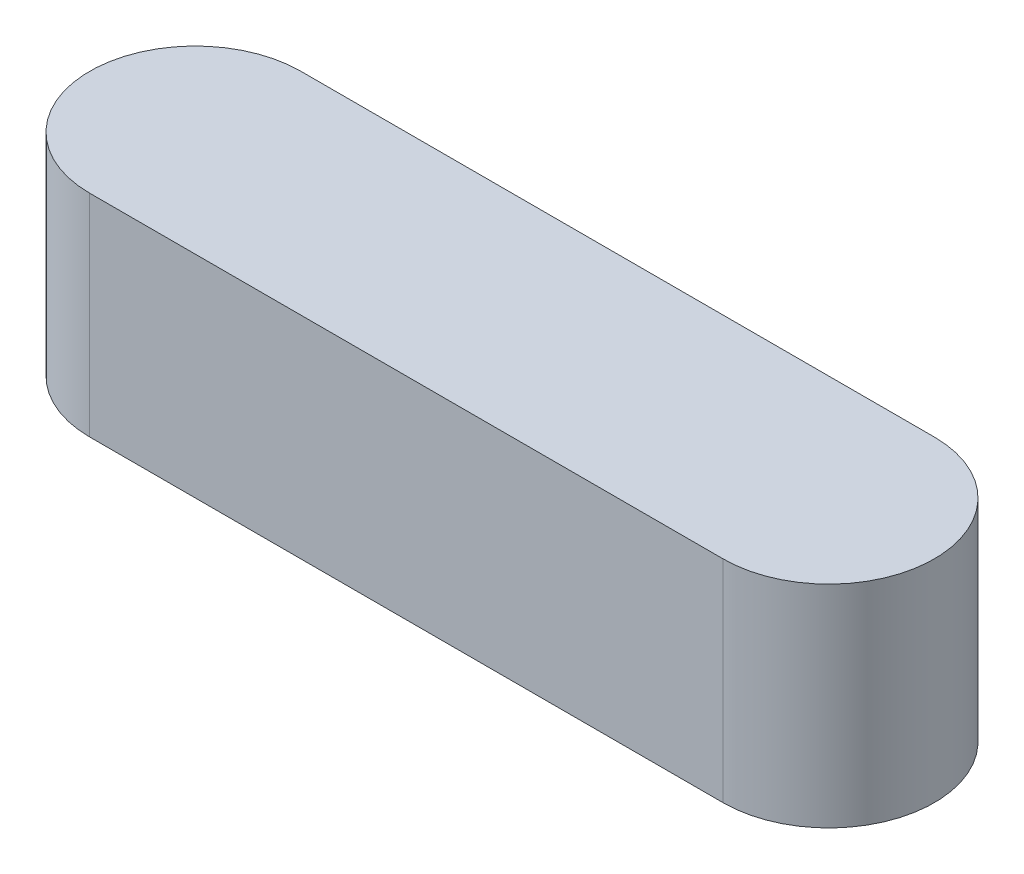
SolidWorks part; units mm, degrees
ref_plane "Front Plane" through (0, 0, 0) normal (0, 0, 1) x (1, 0, 0)
ref_plane "Top Plane" through (0, 0, 0) normal (0, 1, 0) x (1, 0, 0)
ref_plane "Right Plane" through (0, 0, 0) normal (1, 0, 0) x (0, 0, -1)
ref_axis "X AXIS" through (-88.99, 0, 0) along (1, 0, 0)
ref_axis "Y AXIS" through (0, 55, 0) along (0, -1, 0)
ref_axis "Z AXIS" through (0, 0, -88.99) along (0, 0, 1)
sketch "Sketch1" plane through (0, 0, 0) normal (0, 0, 1) x (1, 0, 0)
  line L1 (0, 0) -> (12.7, 0)
  line L2 (0, 0) -> (0, 3.175)
  line L3 (0, 3.175) -> (12.7, 3.175)
  line L4 (12.7, 0) -> (12.7, 3.175)
  dimension "D1" = 3.175
  dimension "D2" = 12.7
extrude "Boss-Extrude1" add sketch "Sketch1" along normal blind 3.175
fillet "Fillet1" 2 edges at (12.7, 1.5875, 3.175) (12.7, 1.5875, 0) type full round first side face at (6.35, 1.5875, 3.175) second side face at (6.35, 1.5875, 0) middle face at (12.7, 1.5875, 1.5875)
fillet "Fillet2" 2 edges at (0, 1.5875, 3.175) (0, 1.5875, 0) type full round first side face at (5.5562, 1.5875, 3.175) second side face at (5.5562, 1.5875, 0) middle face at (0, 1.5875, 1.5875)
